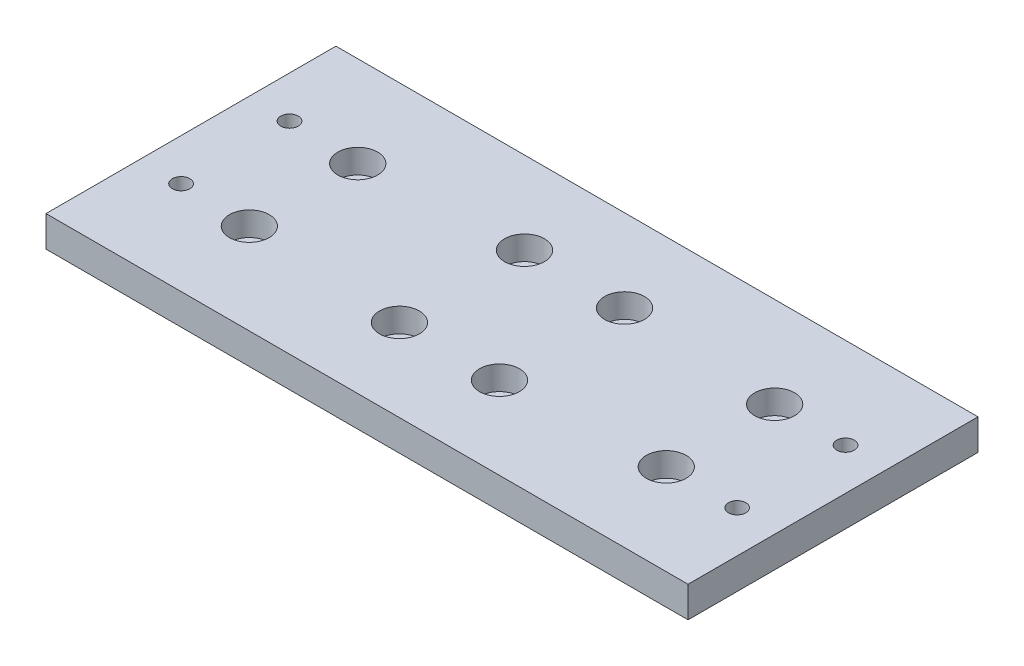
SolidWorks part; units mm, degrees
ref_plane "Plano frontal" through (0, 0, 0) normal (0, 0, 1) x (1, 0, 0)
ref_plane "Plano superior" through (0, 0, 0) normal (0, 1, 0) x (1, 0, 0)
ref_plane "Plano direito" through (0, 0, 0) normal (1, 0, 0) x (0, 0, -1)
sketch "Esboço1" plane through (0, 0, 0) normal (0, 1, 0) x (1, 0, 0)
  line L1 (77, -34.775) -> (-77, -34.775)
  line L2 (77, -34.775) -> (77, 34.775)
  line L3 (77, 34.775) -> (-77, 34.775)
  line L4 (-77, -34.775) -> (-77, 34.775)
  line L5 (77, -34.775) -> (-77, 34.775) construction
  line L6 (77, 34.775) -> (-77, -34.775) construction
  point P0 (0, 0)
  dimension "D1" = 154
  dimension "D2" = 69.55
base flange "Flange-base1" sketch "Esboço1" thickness 7.4 reverse thickness direction no parameters "D1"=10
sketch "Esboço6" plane through (0, 0, 0) normal (0, 1, 0) x (1, 0, 0)
  line L0 (-12, 0) -> (12, 0) construction
  line L3 (0, -34.775) -> (0, 34.775) construction
  line L4 (77, 34.775) -> (-77, 34.775) construction
  line L5 (12, -15) -> (12, 15) construction
  line L6 (-12, -15) -> (-12, 15) construction
  line L7 (-50, 0) -> (50, 0) construction
  line L8 (-50, -13) -> (-50, 13) construction
  line L9 (50, -13) -> (50, 13) construction
  circle A0 centre (-50, 13) radius 4.775
  circle A1 centre (-50, -13) radius 4.775
  circle A2 centre (-12, 15) radius 4.775
  circle A3 centre (12, 15) radius 4.775
  circle A4 centre (12, -15) radius 4.775
  circle A5 centre (50, 13) radius 4.775
  circle A6 centre (50, -13) radius 4.775
  circle A7 centre (-12, -15) radius 4.775
  point P3 (0, 0)
  point P7 (12, 0)
  point P12 (0, 0)
  point P15 (-12, 0)
  point P18 (0, 0)
  point P21 (-50, 0)
  point P24 (50, 0)
extrude "Corte-extrusão1" cut sketch "Esboço6" against normal blind 5.75 normal cut yes
sketch "Esboço8" plane through (0, -5.75, 0) normal (0, 1, 0) x (1, 0, 0)
  circle A0 centre (-50, 13) radius 2.65
  circle A1 centre (-50, -13) radius 2.65
  circle A2 centre (-12, 15) radius 2.65
  circle A3 centre (12, 15) radius 2.65
  circle A4 centre (12, -15) radius 2.65
  circle A5 centre (50, 13) radius 2.65
  circle A6 centre (50, -13) radius 2.65
  circle A7 centre (-12, -15) radius 2.65
extrude "Corte-extrusão3" cut sketch "Esboço8" against normal through all normal cut yes
sketch "Esboço10" plane through (0, 0, 0) normal (0, 1, 0) x (1, 0, 0)
  circle A0 centre (-67, 13.6265) radius 2.1
  circle A1 centre (-67, -12.3735) radius 2.1
  circle A2 centre (67, 13) radius 2.1
  circle A3 centre (67, -13) radius 2.1
extrude "Corte-extrusão4" cut sketch "Esboço10" against normal through all normal cut yes
sketch "Curva-Linhas1" [suppressed] plane through (0, 0, 0) normal (0, 1, 0) x (1, 0, 0)
sketch "Caixa delimitadora1" [suppressed] plane through (0, 0, 0) normal (0, 1, 0) x (1, 0, 0)
sheet metal parameters "Chapa metálica1" thickness 7.4 parameters "D1"=10
flat pattern "Padrão-Plano1" [suppressed]
sketch "Curva-Linhas2" plane through (0, 0, 0) normal (0, 1, 0) x (1, 0, 0)
sketch "Caixa delimitadora2" [suppressed] plane through (0, 0, 0) normal (0, 1, 0) x (1, 0, 0)
sheet metal parameters "Chapa metálica2" thickness 7.4 parameters "D1"=10
flat pattern "Padrão-Plano1"
sketch "Curva-Linhas2" plane through (0, 0, 0) normal (0, 1, 0) x (1, 0, 0)
sketch "Caixa delimitadora2" [suppressed] plane through (0, 0, 0) normal (0, 1, 0) x (1, 0, 0)
sheet metal parameters "Chapa metálica3" thickness 7.4 parameters "D1"=10
flat pattern "Padrão-Plano1"
sketch "Curva-Linhas2" plane through (0, 0, 0) normal (0, 1, 0) x (1, 0, 0)
sketch3d "Caixa delimitadora2" [suppressed]
  line L0 (77, -34.775, 0) -> (-77, -34.775, 0) construction
  line L1 (77, 34.775, 0) -> (-77, 34.775, 0) construction
  line L2 (77, -34.775, 0) -> (77, 34.775, 0) construction
  line L3 (-77, -34.775, 0) -> (-77, 34.775, 0) construction
sheet metal parameters "Chapa metálica4" thickness 7.4 parameters "D1"=10
flat pattern "Padrão-Plano1"
sketch "Curva-Linhas2" plane through (0, 0, 0) normal (0, 1, 0) x (1, 0, 0)
sketch3d "Caixa delimitadora2" [suppressed]
  line L0 (77, -34.775, 0) -> (-77, -34.775, 0) construction
  line L1 (77, 34.775, 0) -> (-77, 34.775, 0) construction
  line L2 (77, -34.775, 0) -> (77, 34.775, 0) construction
  line L3 (-77, -34.775, 0) -> (-77, 34.775, 0) construction
